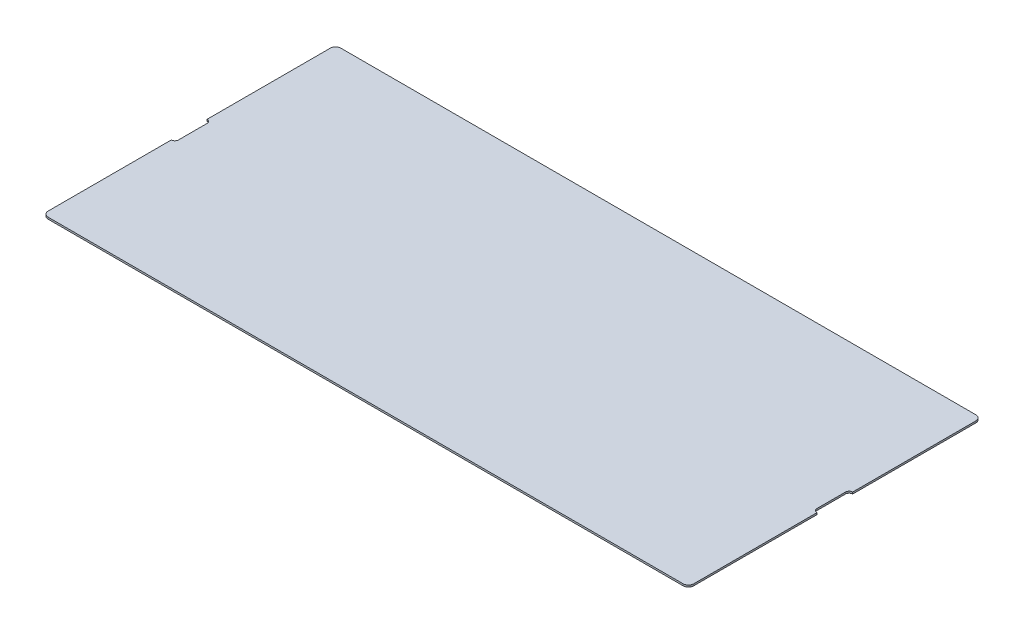
SolidWorks part; units mm, degrees
ref_plane "Front Plane" through (0, 0, 0) normal (0, 0, 1) x (1, 0, 0)
ref_plane "Top Plane" through (0, 0, 0) normal (0, 1, 0) x (1, 0, 0)
ref_plane "Right Plane" through (0, 0, 0) normal (1, 0, 0) x (0, 0, -1)
sketch "Sketch1" plane through (0, 0, 0) normal (0, 1, 0) x (1, 0, 0)
  line L0 (-90.2, 0) -> (90.2, 0) construction
  line L1 (-88.7, 40.9) -> (88.7, 40.9)
  line L2 (-90.2, 39.4) -> (-90.2, -39.4)
  line L3 (-88.7, -40.9) -> (88.7, -40.9)
  line L4 (90.2, 39.4) -> (90.2, -39.4)
  line L5 (-90.2, 40.9) -> (90.2, -40.9) construction
  line L6 (-90.2, -40.9) -> (90.2, 40.9) construction
  line L7 (-90.2, 4) -> (-90.2, -4) construction
  line L8 (-89.2, 4) -> (-89.2, -4)
  line L9 (-91.2, 4) -> (-91.2, -4)
  line L10 (0, 40.9) -> (0, -40.9) construction
  line L11 (90.2, 4) -> (90.2, -4) construction
  line L12 (89.2, 4) -> (89.2, -4)
  line L13 (91.2, 4) -> (91.2, -4)
  arc A0 (88.7, -40.9) -> (90.2, -39.4) centre (88.7, -39.4) ccw
  arc A1 (88.7, 40.9) -> (90.2, 39.4) centre (88.7, 39.4) cw
  arc A2 (-90.2, -39.4) -> (-88.7, -40.9) centre (-88.7, -39.4) ccw
  arc A3 (-88.7, 40.9) -> (-90.2, 39.4) centre (-88.7, 39.4) ccw
  arc A4 (-89.2, 4) -> (-91.2, 4) centre (-90.2, 4) ccw
  arc A5 (-91.2, -4) -> (-89.2, -4) centre (-90.2, -4) ccw
  arc A6 (89.2, 4) -> (91.2, 4) centre (90.2, 4) cw
  arc A7 (91.2, -4) -> (89.2, -4) centre (90.2, -4) cw
  point P0 (0, 0)
  point P22 (-90.2, 0)
  point P31 (90.2, 0)
  dimension "D3" = 1.5
  dimension "D1" = 81.8
  dimension "D2" = 180.4
  dimension "D4" = 8
  dimension "D5" = 2
extrude "Shape" add sketch "Sketch1" along normal blind 0.5 contours L4 A7 L12 A6 A1 L1 A3 L2 A4 L8 A5 A2 L3 A0 region at (0, 0, 0)
